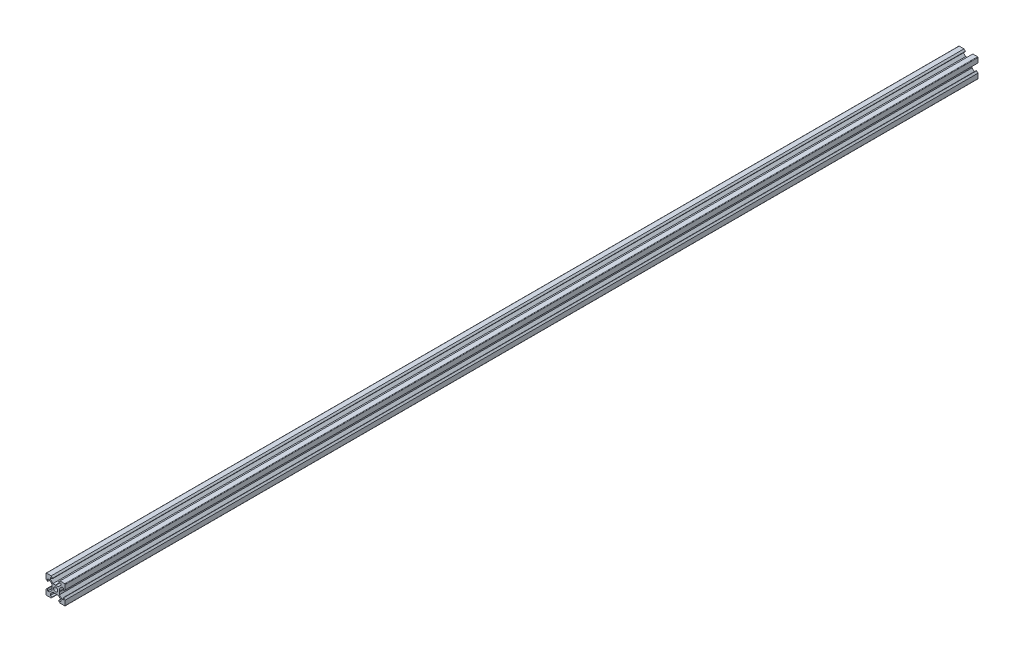
SolidWorks part; units mm, degrees
material "6061-T6 (SS)"
ref_plane "Front Plane" through (0, 0, 0) normal (0, 0, 1) x (1, 0, 0)
ref_plane "Top Plane" through (0, 0, 0) normal (0, 1, 0) x (1, 0, 0)
ref_plane "Right Plane" through (0, 0, 0) normal (1, 0, 0) x (0, 0, -1)
sketch "Sketch1" plane through (0, 0, 0) normal (0, 0, 1) x (1, 0, 0)
  line L1 (9.5, -10) -> (-9.5, -10)
  line L2 (10, -9.5) -> (10, 9.5)
  line L3 (9.5, 10) -> (-9.5, 10)
  line L4 (-10, -9.5) -> (-10, 9.5)
  line L5 (10, -10) -> (-10, 10) construction
  line L6 (10, 10) -> (-10, -10) construction
  circle A0 centre (0, 0) radius 2.1
  arc A1 (-9.5, 10) -> (-10, 9.5) centre (-9.5, 9.5) ccw
  arc A2 (10, 9.5) -> (9.5, 10) centre (9.5, 9.5) ccw
  arc A3 (9.5, -10) -> (10, -9.5) centre (9.5, -9.5) ccw
  arc A4 (-9.5, -10) -> (-10, -9.5) centre (-9.5, -9.5) cw
  point P0 (0, 0)
  line B0 (0, 0) -> (0, 10) construction
  line B1 (0, 3.69) -> (-0.21, 3.9)
  line B2 (-0.21, 3.9) -> (-2.8393, 3.9)
  line B3 (-2.8393, 3.9) -> (-5.5, 6.5607)
  line B4 (-5.5, 6.5607) -> (-5.5, 8.2)
  line B5 (-5.5, 8.2) -> (-3.125, 8.2)
  line B6 (-3.125, 8.2) -> (-3.125, 8.545)
  line B7 (-3.125, 8.545) -> (-4.58, 10)
  line B8 (-4.58, 10) -> (4.58, 10)
  line B9 (0, 0) -> (-5.9132, 5.9132) construction
  line B10 (3.125, 8.545) -> (4.58, 10)
  line B11 (3.125, 8.2) -> (3.125, 8.545)
  line B12 (5.5, 8.2) -> (3.125, 8.2)
  line B13 (5.5, 6.5607) -> (5.5, 8.2)
  line B14 (2.8393, 3.9) -> (5.5, 6.5607)
  line B15 (0.21, 3.9) -> (2.8393, 3.9)
  line B16 (0, 3.69) -> (0.21, 3.9)
  line B17 (0, 0) -> (-10, 0) construction
  line B18 (-3.69, 0) -> (-3.9, -0.21)
  line B19 (-3.9, -0.21) -> (-3.9, -2.8393)
  line B20 (-3.9, -2.8393) -> (-6.5607, -5.5)
  line B21 (-6.5607, -5.5) -> (-8.2, -5.5)
  line B22 (-8.2, -5.5) -> (-8.2, -3.125)
  line B23 (-8.2, -3.125) -> (-8.545, -3.125)
  line B24 (-8.545, -3.125) -> (-10, -4.58)
  line B25 (-10, -4.58) -> (-10, 4.58)
  line B26 (0, 0) -> (-5.9132, -5.9132) construction
  line B27 (-8.545, 3.125) -> (-10, 4.58)
  line B28 (-8.2, 3.125) -> (-8.545, 3.125)
  line B29 (-8.2, 5.5) -> (-8.2, 3.125)
  line B30 (-6.5607, 5.5) -> (-8.2, 5.5)
  line B31 (-3.9, 2.8393) -> (-6.5607, 5.5)
  line B32 (-3.9, 0.21) -> (-3.9, 2.8393)
  line B33 (-3.69, 0) -> (-3.9, 0.21)
  line B34 (0, 0) -> (0, -10) construction
  line B35 (0, -3.69) -> (0.21, -3.9)
  line B36 (0.21, -3.9) -> (2.8393, -3.9)
  line B37 (2.8393, -3.9) -> (5.5, -6.5607)
  line B38 (5.5, -6.5607) -> (5.5, -8.2)
  line B39 (5.5, -8.2) -> (3.125, -8.2)
  line B40 (3.125, -8.2) -> (3.125, -8.545)
  line B41 (3.125, -8.545) -> (4.58, -10)
  line B42 (4.58, -10) -> (-4.58, -10)
  line B43 (0, 0) -> (5.9132, -5.9132) construction
  line B44 (-3.125, -8.545) -> (-4.58, -10)
  line B45 (-3.125, -8.2) -> (-3.125, -8.545)
  line B46 (-5.5, -8.2) -> (-3.125, -8.2)
  line B47 (-5.5, -6.5607) -> (-5.5, -8.2)
  line B48 (-2.8393, -3.9) -> (-5.5, -6.5607)
  line B49 (-0.21, -3.9) -> (-2.8393, -3.9)
  line B50 (0, -3.69) -> (-0.21, -3.9)
  line B51 (0, 0) -> (10, 0) construction
  line B52 (3.69, 0) -> (3.9, 0.21)
  line B53 (3.9, 0.21) -> (3.9, 2.8393)
  line B54 (3.9, 2.8393) -> (6.5607, 5.5)
  line B55 (6.5607, 5.5) -> (8.2, 5.5)
  line B56 (8.2, 5.5) -> (8.2, 3.125)
  line B57 (8.2, 3.125) -> (8.545, 3.125)
  line B58 (8.545, 3.125) -> (10, 4.58)
  line B59 (10, 4.58) -> (10, -4.58)
  line B60 (0, 0) -> (5.9132, 5.9132) construction
  line B61 (8.545, -3.125) -> (10, -4.58)
  line B62 (8.2, -3.125) -> (8.545, -3.125)
  line B63 (8.2, -5.5) -> (8.2, -3.125)
  line B64 (6.5607, -5.5) -> (8.2, -5.5)
  line B65 (3.9, -2.8393) -> (6.5607, -5.5)
  line B66 (3.9, -0.21) -> (3.9, -2.8393)
  line B67 (3.69, 0) -> (3.9, -0.21)
  dimension "D1" = 4.2
  dimension "D3" = 0.5
  dimension "D2" = 20
sketch_block_instance "V Slot 1-4"
sketch_block "V Slot 1" parameters "D1"=10, "D2"=11, "D3"=4.3, "D4"=1.8, "D5"=0.21, "D6"=45, "D7"=9.16, "D8"=1.5, "D9"=6.25
sketch_block_instance "V Slot 1-5"
sketch_block_instance "V Slot 1-6"
sketch_block_instance "V Slot 1-7"
extrude "Boss-Extrude1" add sketch "Sketch1" along normal blind 948.5 contours B67 B52 B53 B54 B55 B56 B57 B58 L2 A2 L3 B10 B11 B12 B13 B14 B15 B16 B1 B2 B3 B4 B5 B6 B7 A1 L4 B27 B28 B29 B30 B31 B32 B33 B18 B19 B20 B21 B22 B23 B24 A4 L1 B44 B45 B46 B47 B48 B49 region at (7.04, -9.7172, 0)
